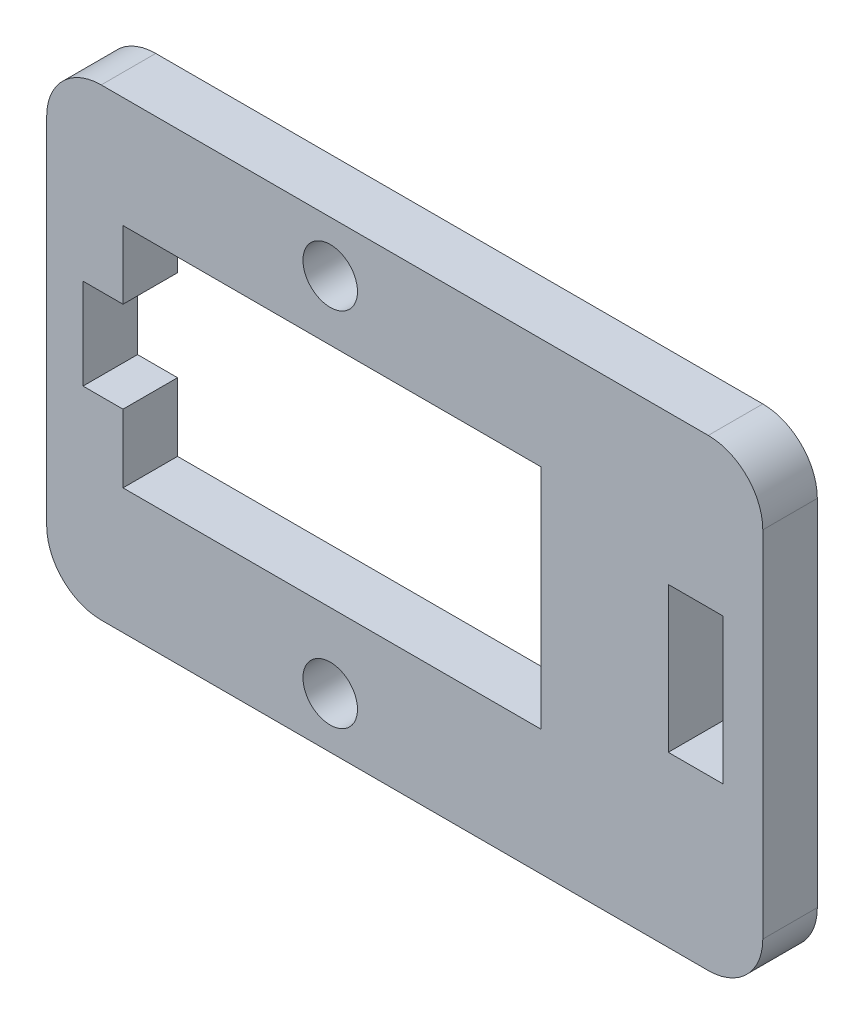
SolidWorks part; units mm, degrees
ref_plane "Plan de face" through (0, 0, 0) normal (0, 0, 1) x (1, 0, 0)
ref_plane "Plan de dessus" through (0, 0, 0) normal (0, 1, 0) x (1, 0, 0)
ref_plane "Plan de droite" through (0, 0, 0) normal (1, 0, 0) x (0, 0, -1)
sketch "Esquisse1" plane through (0, 0, 0) normal (0, 0, 1) x (1, 0, 0)
  line L0 (853.4016, 1994.0129) -> (892.788, 1995.0472) construction
  line L1 (853.5431, 2007.8358) -> (892.9431, 2007.8358)
  line L2 (853.5431, 1982.3358) -> (892.9431, 1982.3358)
  line L3 (892.9431, 1982.3358) -> (892.9431, 2007.8358)
  line L4 (853.5431, 2007.8358) -> (853.5431, 1982.3358)
  line L5 (857.7431, 1997.9858) -> (855.5431, 1997.9858)
  line L6 (857.7431, 2001.7358) -> (880.7431, 2001.7358)
  line L7 (857.7431, 2001.7358) -> (857.7431, 1989.2358) construction
  line L8 (857.7431, 1989.2358) -> (880.7431, 1989.2358)
  line L9 (880.7431, 2001.7358) -> (880.7431, 1989.2358)
  line L10 (855.5431, 1997.9858) -> (855.5431, 1992.9858)
  line L11 (855.5431, 1992.9858) -> (857.7431, 1992.9858)
  line L12 (880.7431, 1995.4858) -> (857.7431, 1995.4858) construction
  line L13 (857.7431, 2001.7358) -> (857.7431, 1997.9858)
  line L14 (857.7431, 1992.9858) -> (857.7431, 1989.2358)
  line L15 (869.2431, 1989.2358) -> (869.2431, 2005.6396) construction
  line L17 (887.7431, 1999.6358) -> (890.7431, 1999.6358)
  line L18 (887.7431, 1999.6358) -> (887.7431, 1991.6358)
  line L19 (887.7431, 1991.6358) -> (890.7431, 1991.6358)
  line L20 (890.7431, 1999.6358) -> (890.7431, 1991.6358)
  circle A0 centre (869.1431, 2005.0358) radius 1.5
  circle A1 centre (869.1431, 1985.1356) radius 1.5
  dimension "D13" = 3
  dimension "D14" = 3
  dimension "D17" = 22.3
  dimension "D1" = 39.4
  dimension "D2" = 25.5
  dimension "D3" = 2007.8358
  dimension "D4" = 39.4
  dimension "D5" = 892.9431
  dimension "D6" = 12.5
  dimension "D7" = 23
  dimension "D8" = 6.1
  dimension "D9" = 12.2
  dimension "D10" = 2
  dimension "D11" = 5
  dimension "D12" = 2.5
  dimension "D15" = 1.3
  dimension "D16" = 1.2998
  dimension "D18" = 22.3
  dimension "D19" = 3
  dimension "D20" = 8
  dimension "D21" = 2.2
  dimension "D22" = 9.3
base flange "Tôle de base pliée1" sketch "Esquisse1" thickness 3 reverse thickness direction no parameters "D1"=1.5
fillet "Congé1" radius 3 4 edges at (853.5431, 1982.3358, -1.5) (892.9431, 1982.3358, -1.5) (892.9431, 2007.8358, -1.5) (853.5431, 2007.8358, -1.5)
sketch "Lignes de pliage1" [suppressed] plane through (0, 0, 0) normal (0, 1, 0) x (1, 0, 0)
sketch "Cube de visualisation1" [suppressed] plane through (0, 0, 0) normal (0, 1, 0) x (1, 0, 0)
sheet metal parameters "Tôlerie1" thickness 3 parameters "D1"=1.5
flat pattern "Etat déplié1" [suppressed]
sketch "Lignes de pliage2" plane through (0, 0, 0) normal (0, 1, 0) x (1, 0, 0)
sketch3d "Cube de visualisation2" [suppressed]
  line L0 (853.5431, 2007.8358, 0) -> (892.9431, 2007.8358, 0) construction
  line L1 (853.5431, 1982.3358, 0) -> (892.9431, 1982.3358, 0) construction
  line L2 (853.5431, 2007.8358, 0) -> (853.5431, 1982.3358, 0) construction
  line L3 (892.9431, 2007.8358, 0) -> (892.9431, 1982.3358, 0) construction
